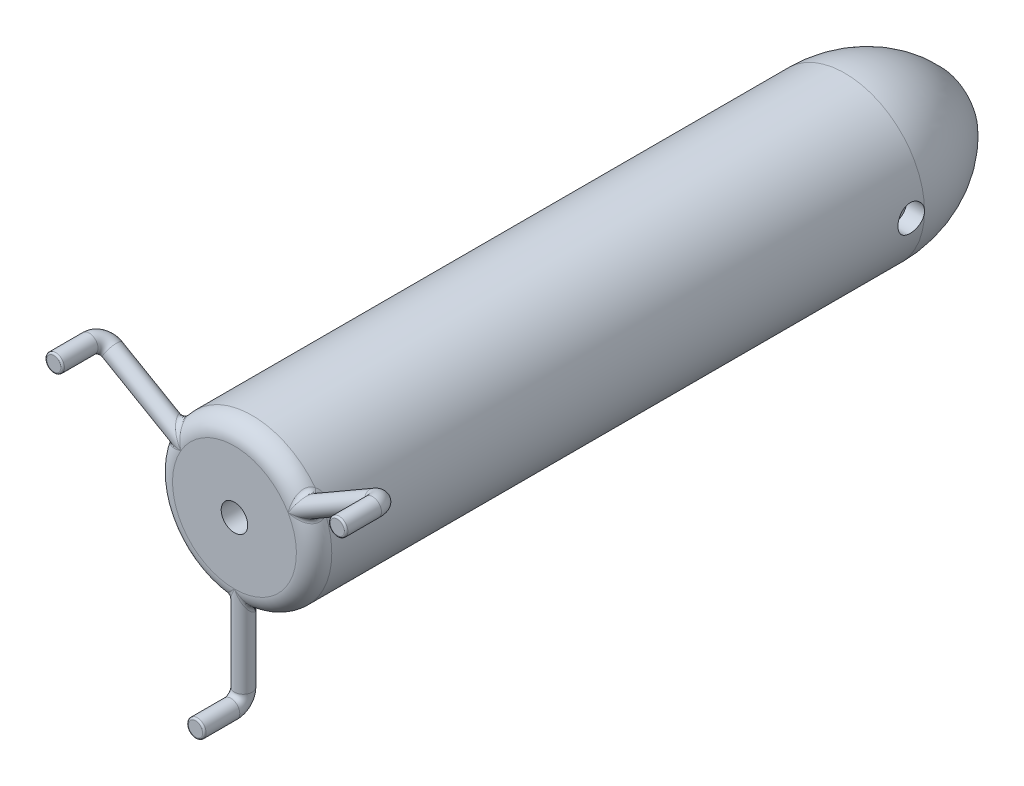
SolidWorks part; units mm, degrees
note: The reader was unsure of these and kept them because the rebuilt part matched: shared geometry of "Arm Profile Sketch<2>".
ref_plane "Front Plane" through (0, 0, 0) normal (0, 0, 1) x (1, 0, 0)
ref_plane "Top Plane" through (0, 0, 0) normal (0, 1, 0) x (1, 0, 0)
ref_plane "Right Plane" through (0, 0, 0) normal (1, 0, 0) x (0, 0, -1)
sketch "Body Sketch" plane through (0, 0, 0) normal (1, 0, 0) x (0, 0, -1)
  line L0 (0, 0) -> (55, 0)
  line L1 (-345, 45) -> (0, 45)
  line L2 (-345, 45) -> (-345, 0)
  line L3 (-345, 0) -> (0, 0)
  line L7 (55, 20) -> (55, 0)
  arc A0 (55, 20) -> (0, 45) centre (0, -28) ccw
  dimension "D1" = 45
  dimension "D2" = 400
  dimension "D3" = 55
  dimension "D4" = 20
revolve "Body Revolve" add sketch "Body Sketch" angle 360 about L3
fillet "Large Face Fillet" radius 10 1 edges at (45, 0, 345)
fillet "Small Face Fillet" radius 3 1 edges at (20, 0, -55)
sketch "Shaft Sketch" plane through (0, 0, 345) normal (0, 0, 1) x (1, 0, 0)
  circle A0 centre (0, 0) radius 7.5
  dimension "D1" = 15
extrude "Shaft Cut" cut sketch "Shaft Sketch" against normal blind 80
ref_plane "Electronics Cut Plane" through (45, 0, 0) normal (1, 0, 0) x (0, 0, -1)
sketch "Electronics Sketch" plane through (45, 0, 0) normal (1, 0, 0) x (0, 0, -1)
  line L0 (-7.5, 7.5) -> (-7.5, 45) construction
  line L1 (0, 45) -> (-335, 45) construction
  line L2 (-7.5, -7.5) -> (-7.5, -45) construction
  line L3 (-335, -45) -> (0, -45) construction
  line L5 (0, 45) -> (0, -45) construction
  circle A0 centre (-7.5, 0) radius 7.5
  dimension "D1" = 15
  dimension "D2" = 7.5
extrude "Electronics Cut" cut sketch "Electronics Sketch" against normal blind 10
sketch "Arm Sweep Sketch" plane through (0, 0, 0) normal (1, 0, 0) x (0, 0, -1)
  line L0 (-340, -45) -> (-340, -85.5)
  line L1 (-335, -45) -> (0, -45) construction
  line L2 (-367, -92.5) -> (-347, -92.5)
  line L3 (-335, -45) -> (-345, -45) construction
  line L4 (-335, 45) -> (-335, -45) construction
  line L5 (-345, 35) -> (-345, -35) construction
  line L6 (-345, 0) -> (0, 0) construction
  arc A0 (-347, -92.5) -> (-340, -85.5) centre (-347, -85.5) ccw
  point P5 (-340, -45)
  dimension "D1" = 7
  dimension "D2" = 92.5
  dimension "D3" = 20
ref_plane "Arm Plane" through (0, -45, 0) normal (0, 1, 0) x (1, 0, 0)
sketch "Arm Profile Sketch" plane through (0, -45, 0) normal (0, 1, 0) x (1, 0, 0)
  circle A0 centre (0, -340) radius 5
sweep "Arm Sweep" add profiles "Arm Profile Sketch" path "Arm Sweep Sketch"
extrude "Arm Extrude" add sketch "Arm Profile Sketch<2>" along normal up to surface (10 mm away)
sketch "Arm Profile Sketch<2>" plane through (0, -45, 0) normal (0, 1, 0) x (1, 0, 0) same geometry as "Arm Profile Sketch"
fillet "Arm Center Fillet" radius 3 2 edges at (4.8706, -43.9518, 338.87) (4.8706, -43.9518, 338.87)
fillet "Arm Outer Fillet" radius 1 1 edges at (0, -87.5, 367)
pattern_circular "Arm Pattern" count 3 over 360 about axis through (0, 0, 345) along (0, 0, -1) of "Arm Sweep", "Arm Extrude", "Arm Center Fillet", "Arm Outer Fillet"
